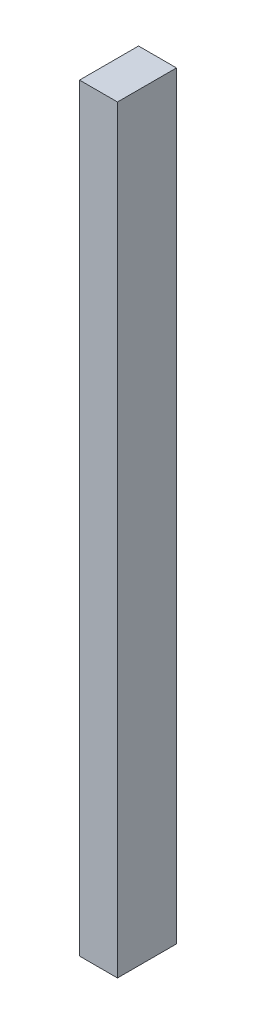
SolidWorks part; units mm, degrees
material "Pine"
ref_plane "Front Plane" through (0, 0, 0) normal (0, 0, 1) x (1, 0, 0)
ref_plane "Top Plane" through (0, 0, 0) normal (0, 1, 0) x (1, 0, 0)
ref_plane "Right Plane" through (0, 0, 0) normal (1, 0, 0) x (0, 0, -1)
sketch "Sketch1" plane through (0, 0, 0) normal (0, 1, 0) x (1, 0, 0)
  line L1 (0, 0) -> (45, 0)
  line L2 (0, 0) -> (0, 70)
  line L3 (0, 70) -> (45, 70)
  line L4 (45, 0) -> (45, 70)
  dimension "D1" = 70
  dimension "D2" = 45
extrude "Boss-Extrude1" add sketch "Sketch1" along normal blind 900
